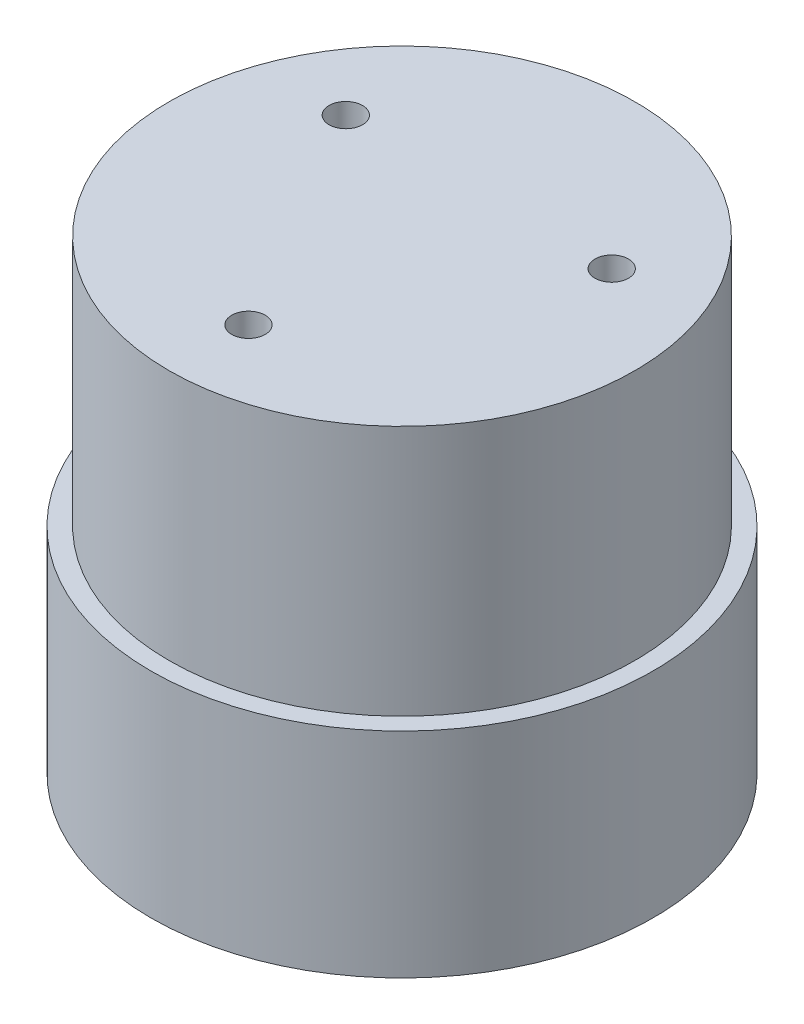
SolidWorks part; units mm, degrees
ref_plane "Front Plane" through (0, 0, 0) normal (0, 0, 1) x (1, 0, 0)
ref_plane "Top Plane" through (0, 0, 0) normal (0, 1, 0) x (1, 0, 0)
ref_plane "Right Plane" through (0, 0, 0) normal (1, 0, 0) x (0, 0, -1)
sketch "Sketch2" plane through (0, 0, 0) normal (0, 1, 0) x (1, 0, 0)
  circle A0 centre (0, 0) radius 27
  dimension "D1" = 54
extrude "Boss-Extrude2" add sketch "Sketch2" along normal blind 50
sketch "Sketch6" plane through (0, 0, 0) normal (0, -1, 0) x (-1, 0, 0)
  line L0 (-14.2981, 8.255) -> (0, 0) construction
  line L1 (0, 0) -> (14.2981, 8.255) construction
  line L3 (0, 0) -> (0, -16.51) construction
  point P0 (0, -16.51)
  point P2 (-14.2981, 8.255)
  point P4 (14.2981, 8.255)
  dimension "D1" = 16.51
  dimension "D2" = 120
  dimension "D3" = 120
hole_wizard "CBORE for M3 SHCS1" positions "Sketch6" profile "Sketch5" counterbore size "M3" standard "ANSI Metric" end condition through all
sketch "Sketch5" plane through (0, 0, 16.51) normal (1, 0, 0) x (0, 0, -1)
  line L0 (0, 0) -> (0, 50)
  line L1 (0, 50) -> (1.8, 50)
  line L3 (1.8, 50) -> (1.8, 43)
  line L4 (3.25, 43) -> (1.8, 43)
  line L5 (3.25, 43) -> (3.25, 0.025)
  line L6 (3.25, 0.025) -> (3.275, 0)
  line L7 (3.275, 0) -> (0, 0)
  line L8 (-3.25, 0.025) -> (-3.275, 0) construction
  line L11 (0, -6.35) -> (0, 107.95) construction
  dimension "Thru Hole Dia." = 3.6
  dimension "Thru Hole Depth" = 50
  dimension "C'Bore Dia." = 6.5
  dimension "C'Bore Depth" = 43
  dimension "Near C'Sink Dia." = 6.55
  dimension "Near C'Sink Angle" = 90
sketch "Sketch9" plane through (0, 0, 0) normal (0, -1, 0) x (-1, 0, 0)
  line L0 (-14.2981, -8.255) -> (0, 0) construction
  line L1 (0, 0) -> (0, 16.51) construction
  line L2 (0, 0) -> (14.2981, -8.255) construction
  point P0 (14.2981, -8.255)
  point P2 (0, 16.51)
  point P4 (-14.2981, -8.255)
  dimension "D1" = 120
  dimension "D2" = 120
  dimension "D3" = 16.51
hole_wizard "Hole1" positions "Sketch9" profile "Sketch8" legacy
sketch "Sketch8" plane through (-14.2981, 0, 8.255) normal (1, 0, 0) x (0, 0, -1)
  line L0 (0, 0) -> (0, 15)
  line L1 (0, 15) -> (3.2, 15)
  line L2 (3.2, 15) -> (3.2, 2)
  line L3 (3.2, 2) -> (3.65, 2)
  line L4 (3.65, 2) -> (3.65, 0)
  line L5 (3.65, 0) -> (0, 0)
  line L6 (0, 110) -> (0, -10) construction
  dimension "Diameter" = 6.4
  dimension "Depth" = 15
  dimension "C-Bore Diameter" = 7.3
  dimension "C-Bore Depth" = 2
chamfer "Chamfer1" distance 2 distance2 0.45 3 edges at (-14.2981, 2, 4.605) (0, 2, -20.16) (14.2981, 2, 4.605) first distance on face at (-14.2981, 2, 4.605) first distance on face at (0, 2, -20.16) first distance on face at (14.2981, 2, 4.605)
sketch "Sketch10" plane through (0, 50, 0) normal (0, 1, 0) x (1, 0, 0)
  circle A0 centre (0, 0) radius 25.05
  circle A1 centre (0, 0) radius 27
  dimension "D1" = 50.1
extrude "Cut-Extrude1" cut sketch "Sketch10" against normal offset from surface (27 mm away) 23 up to face at (-14.2981, 0, 4.605)
